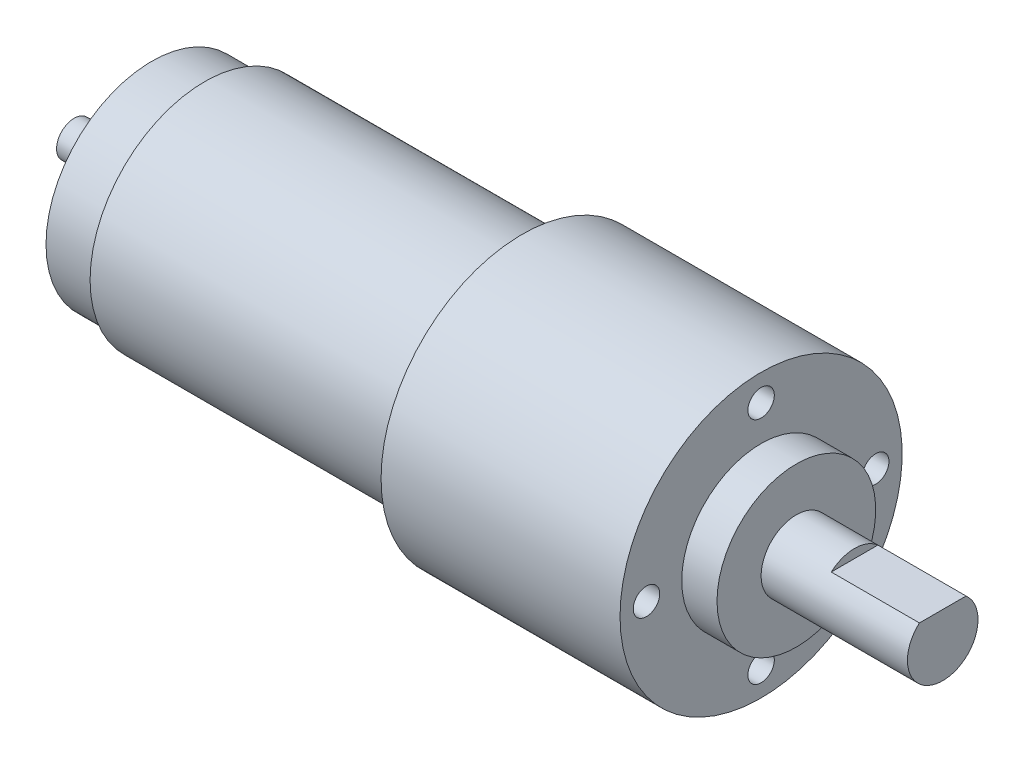
SolidWorks part; units mm, degrees
ref_plane "Plan de face" through (0, 0, 0) normal (0, 0, 1) x (1, 0, 0)
ref_plane "Plan de dessus" through (0, 0, 0) normal (0, 1, 0) x (1, 0, 0)
ref_plane "Plan de droite" through (0, 0, 0) normal (1, 0, 0) x (0, 0, -1)
ref_axis "Axe1" through (-5.325, 0, 0) along (1, 0, 0)
sketch "Esquisse1" plane through (0, 0, 0) normal (0, 0, 1) x (1, 0, 0)
  line L0 (0, 0) -> (98.5, 0)
  line L1 (98.5, 0) -> (98.5, 4)
  line L2 (98.5, 4) -> (81.9, 4)
  line L3 (81.9, 4) -> (81.9, 9)
  line L4 (81.9, 9) -> (77.9, 9)
  line L5 (77.9, 9) -> (77.9, 16)
  line L6 (77.9, 16) -> (50.8, 16)
  line L7 (50.8, 16) -> (50.8, 13)
  line L8 (50.8, 13) -> (14.8, 13)
  line L9 (14.8, 13) -> (14.8, 12)
  line L10 (14.8, 12) -> (8.8, 12)
  line L11 (8.8, 12) -> (8.8, 2)
  line L12 (8.8, 2) -> (0, 2)
  line L13 (0, 2) -> (0, 0)
  dimension "D1" = 27.1
  dimension "D2" = 4
  dimension "D3" = 20.6
  dimension "D4" = 13
  dimension "D5" = 16
  dimension "D6" = 9
  dimension "D7" = 12
  dimension "D8" = 2
  dimension "D9" = 42
  dimension "D10" = 6
  dimension "D11" = 8.8
  dimension "D12" = 4
  dimension "D13" = 98.5
revolve "MainRevolution" add sketch "Esquisse1" angle 360 about L0
sketch "Esquisse2" plane through (98.5, 0, 0) normal (1, 0, 0) x (0, 0, -1)
  line L1 (-2.6458, 3) -> (2.6458, 3)
  line L2 (-2.6458, 3) -> (-2.6458, 4)
  line L3 (-2.6458, 4) -> (2.6458, 4)
  line L4 (2.6458, 3) -> (2.6458, 4)
  circle A0 centre (0, 0) radius 4 construction
  circle A1 centre (0, 0) radius 4 construction
  dimension "D1" = 1
extrude "Enlèv. mat.-Extru.1" cut sketch "Esquisse2" against normal blind 10
sketch "Esquisse3" plane through (77.9, 0, 0) normal (1, 0, 0) x (0, 0, -1)
  line L0 (0, 55) -> (0, -55) construction
  circle A0 centre (0, 13) radius 1.5
  circle A1 centre (0, 0) radius 16 construction
  dimension "D1" = 3
  dimension "D2" = 13
extrude "FixHoles" cut sketch "Esquisse3" against normal blind 3
pattern_circular "RepeatFixHoles" count 4 every 90 about axis through (-5.325, 0, 0) along (1, 0, 0) of "FixHoles"
